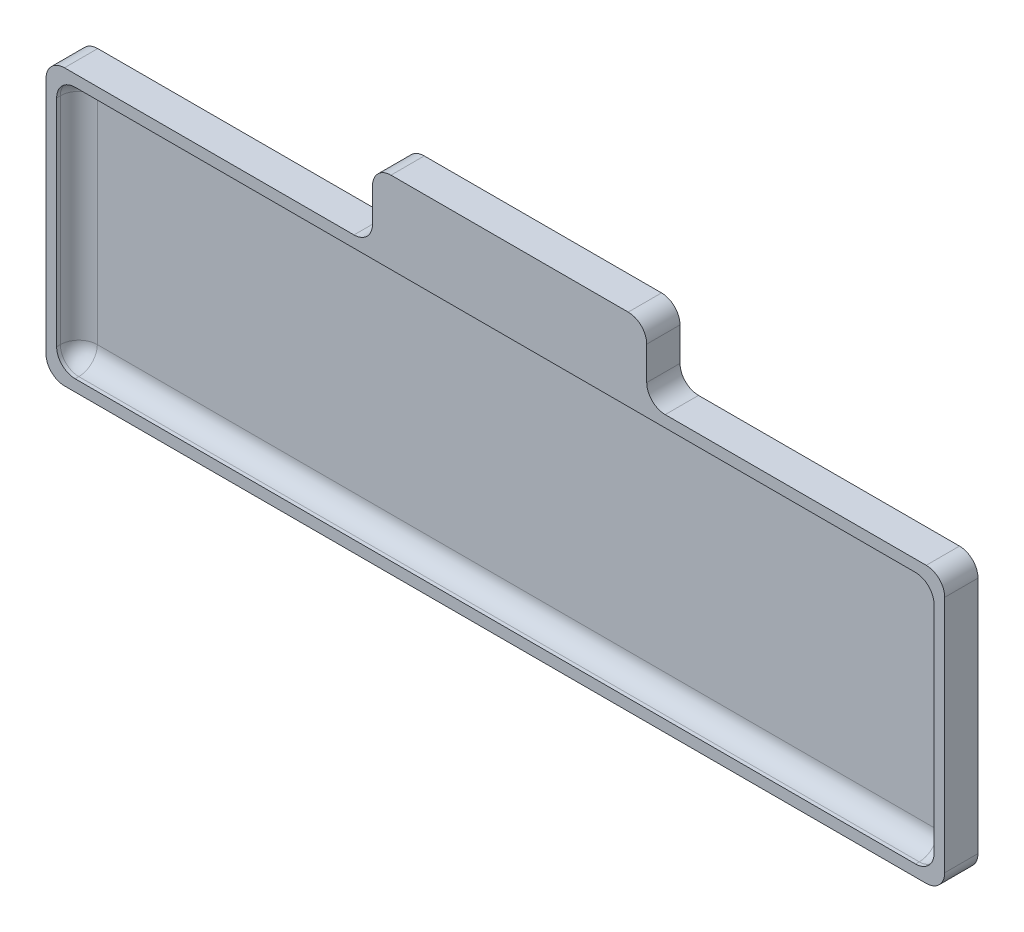
SolidWorks part; units mm, degrees
ref_plane "Front Plane" through (0, 0, 0) normal (0, 0, 1) x (1, 0, 0)
ref_plane "Top Plane" through (0, 0, 0) normal (0, 1, 0) x (1, 0, 0)
ref_plane "Right Plane" through (0, 0, 0) normal (1, 0, 0) x (0, 0, -1)
sketch "Sketch2" plane through (0, 0, 0) normal (0, 0, 1) x (1, 0, 0)
  line L0 (-114.9155, 82.8249) -> (-117.7932, 85.9424)
  line L1 (-117.7932, 85.9424) -> (125.2068, 85.9424)
  line L2 (-117.7932, 85.9424) -> (-117.7932, 11.4424)
  line L3 (-117.7932, 11.4424) -> (125.2068, 11.4424)
  line L4 (125.2068, 85.9424) -> (125.2068, 11.4424)
  line L5 (-114.9155, 82.8249) -> (122.3291, 82.8249)
  line L6 (-114.9155, 82.8249) -> (-114.9155, 14.5599)
  line L7 (-114.9155, 14.5599) -> (122.3291, 14.5599)
  line L8 (122.3291, 82.8249) -> (122.3291, 14.5599)
  line L9 (122.3291, 82.8249) -> (125.2068, 85.9424)
  line L10 (122.3291, 14.5599) -> (125.2068, 11.4424)
  dimension "D1" = 243
  dimension "D2" = 74.5
  dimension "D3" = 4.2426
extrude "Boss-Extrude1" add sketch "Sketch2" along normal blind 3 contours L8 L5 L6 L7 | L5 L9 L1 L0 | L8 L10 L4 L9 | L10 L7 L6 L0 L2 L3 region at (-117.4572, 48.6924, 0) region at (3.7068, 84.3898, 0) region at (3.7068, 48.6924, 0) region at (123.7889, 48.6924, 0)
extrude "Boss-Extrude2" add sketch "Sketch2<3>" along normal blind 9 contours L5 L9 L1 L0 | L8 L10 L4 L9 | L10 L7 L6 L0 L2 L3 region at (-117.4572, 48.6924, 0) region at (3.7068, 84.3898, 0) region at (123.7889, 48.6924, 0)
sketch "Sketch2<3>" plane through (0, 0, 0) normal (0, 0, 1) x (1, 0, 0) same geometry as "Sketch2"
sketch "Sketch3" plane through (0, 85.9424, 0) normal (0, 1, 0) x (1, 0, 0)
  line L0 (-117.7932, 0) -> (125.2068, 0) construction
  line L5 (-29.5156, 0) -> (44.6347, 0)
  line L6 (-29.5156, 0) -> (-29.5156, -9)
  line L7 (-29.5156, -9) -> (44.6347, -9)
  line L8 (44.6347, 0) -> (44.6347, -9)
  line L9 (-117.7932, -9) -> (125.2068, -9) construction
extrude "Boss-Extrude4" add sketch "Sketch3" along normal blind 19
fillet "Fillet1" radius 5 16 edges at (3.7068, 82.8249, 3) (-114.9155, 48.6924, 3) (3.7068, 14.5599, 3) (122.3291, 48.6924, 3) (44.6347, 85.9424, 4.5) (-29.5156, 85.9424, 4.5) (-29.5156, 104.9424, 4.5) (44.6347, 104.9424, 4.5) (122.3291, 82.8249, 6) (125.2068, 85.9424, 4.5) (122.3291, 14.5599, 6) (125.2068, 11.4424, 4.5) (-114.9155, 14.5599, 6) (-114.9155, 82.8249, 6) (-117.7932, 11.4424, 4.5) (-117.7932, 85.9424, 4.5)
